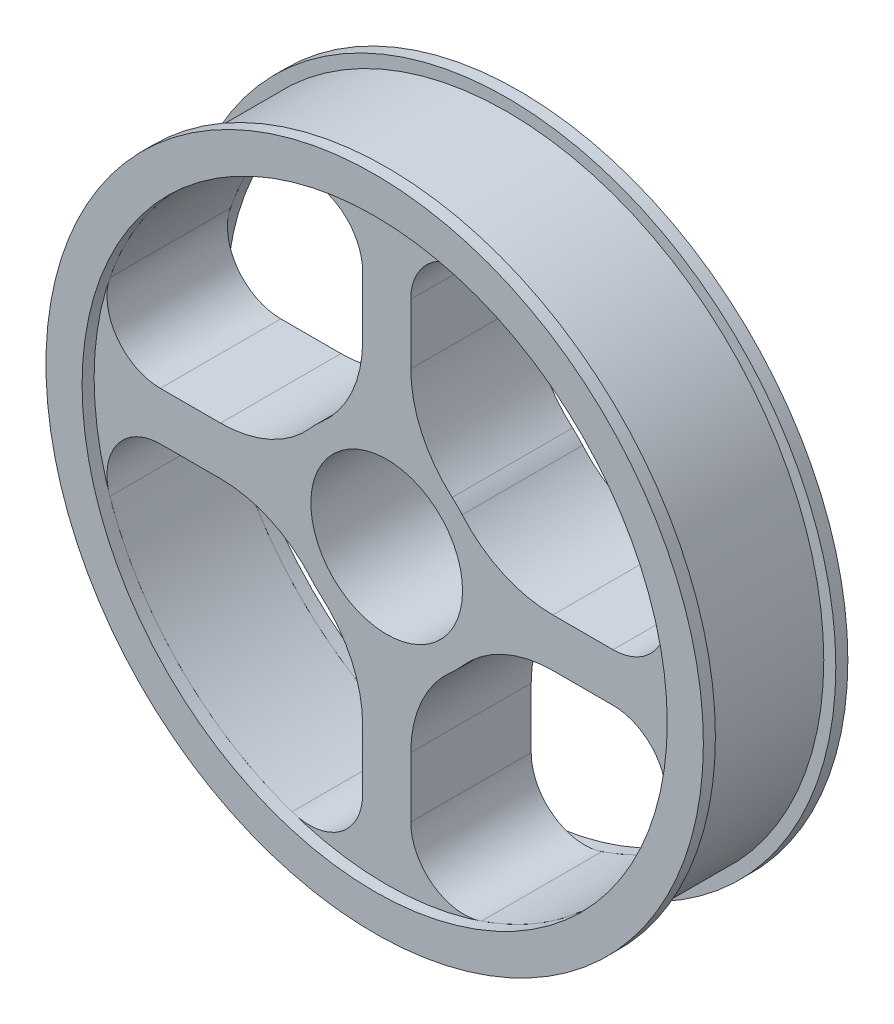
SolidWorks part; units mm, degrees
material "ABS"
ref_plane "Front Plane" through (0, 0, 0) normal (0, 0, 1) x (1, 0, 0)
ref_plane "Top Plane" through (0, 0, 0) normal (0, 1, 0) x (1, 0, 0)
ref_plane "Right Plane" through (0, 0, 0) normal (1, 0, 0) x (0, 0, -1)
sketch "Sketch1" plane through (0, 0, 0) normal (0, 0, 1) x (1, 0, 0)
  line L0 (-14.5852, 8.4694) -> (-14.5852, 12.5334) construction
  line L2 (-14.0772, 11.1364) -> (-14.0772, 9.8664)
  line L4 (-15.0932, 11.1364) -> (-15.0932, 9.8664)
  line L5 (-9.8102, 6.8694) -> (-11.0802, 6.8694)
  line L6 (-14.5852, 10.5014) -> (-15.0932, 10.5014) construction
  line L7 (-9.8102, 5.8534) -> (-11.0802, 5.8534)
  line L8 (-14.0772, 1.5864) -> (-14.0772, 2.8564)
  line L9 (-15.0932, 1.5864) -> (-15.0932, 2.8564)
  line L10 (-19.3602, 5.8534) -> (-18.0902, 5.8534)
  line L11 (-19.3602, 6.8694) -> (-18.0902, 6.8694)
  circle A1 centre (-14.5852, 6.3614) radius 2.108
  circle A5 centre (-14.5852, 6.3614) radius 6.172
  circle A6 centre (-14.5852, 6.3614) radius 1.6
  circle A7 centre (-14.5852, 6.3614) radius 6.68
  circle A8 centre (-14.5852, 6.3614) radius 6.934
  arc A9 (-15.0932, 11.1364) -> (-16.5828, 12.2012) centre (-16.2185, 11.1364) ccw
  arc A10 (-15.0932, 9.8664) -> (-15.9661, 7.9541) centre (-17.6242, 9.8664) cw
  arc A11 (-14.0772, 9.8664) -> (-13.2042, 7.9541) centre (-11.5461, 9.8664) ccw
  arc A12 (-14.0772, 11.1364) -> (-12.5876, 12.2012) centre (-12.9518, 11.1364) cw
  arc A13 (-11.0802, 6.8694) -> (-12.9925, 7.7424) centre (-11.0802, 9.4005) cw
  arc A14 (-9.8102, 6.8694) -> (-8.7454, 8.359) centre (-9.8102, 7.9948) ccw
  arc A15 (-9.8102, 5.8534) -> (-8.7454, 4.3638) centre (-9.8102, 4.728) cw
  arc A16 (-11.0802, 5.8534) -> (-12.9925, 4.9804) centre (-11.0802, 3.3223) ccw
  arc A17 (-14.0772, 2.8564) -> (-13.2042, 4.7687) centre (-11.5461, 2.8564) cw
  arc A18 (-14.0772, 1.5864) -> (-12.5876, 0.5216) centre (-12.9518, 1.5864) ccw
  arc A19 (-15.0932, 1.5864) -> (-16.5828, 0.5216) centre (-16.2185, 1.5864) cw
  arc A20 (-15.0932, 2.8564) -> (-15.9661, 4.7687) centre (-17.6242, 2.8564) ccw
  arc A21 (-18.0902, 5.8534) -> (-16.1779, 4.9804) centre (-18.0902, 3.3223) cw
  arc A22 (-19.3602, 5.8534) -> (-20.425, 4.3638) centre (-19.3602, 4.728) ccw
  arc A23 (-19.3602, 6.8694) -> (-20.425, 8.359) centre (-19.3602, 7.9948) cw
  arc A24 (-18.0902, 6.8694) -> (-16.1779, 7.7424) centre (-18.0902, 9.4005) ccw
  circle A27 centre (-14.5852, 6.3614) radius 1.6 construction
  point P4 (-15.9228, 6.2618)
  point P22 (-13.5497, 5.29)
  point P64 (-14.5852, 6.3614)
  dimension "D1" = 0.508
  dimension "D2" = 0.508
  dimension "D3" = 5.08
  dimension "D4" = 0.254
  dimension "D5" = 0.508
  dimension "D6" = 1.27
  dimension "D7" = 4
extrude "Boss-Extrude1" add sketch "Sketch1" along normal mid plane 2.54 contours A7 A5 | L2 A12 A5 A9 L4 A10 A1 A11 | A16 L7 A15 A5 A14 L5 A13 A1 | A24 L11 A23 A5 A22 L10 A21 A1 | A20 L9 A19 A5 A18 L8 A17 A1 | A1 A6 region at (-14.5852, 10.5868, 0) region at (-13.1368, 7.8098, 0) region at (-10.3598, 6.3614, 0) region at (-18.8106, 6.3614, 0) region at (-14.5852, 2.136, 0) region at (-21.0762, 6.3614, 0)
extrude "Boss-Extrude2" add sketch "Sketch1<5>" along normal blind 0.254 from surface separate body contours A7 A5 | A8 A7 region at (-21.0762, 6.3614, 0) region at (-21.3231, 6.3614, 0) starting at face at (-12.0398, 3.816, 1.27)
sketch "Sketch1<5>" plane through (0, 0, 0) normal (0, 0, 1) x (1, 0, 0) same geometry as "Sketch1"
mirror "Mirror2" about plane through (0, 0, 0) normal (0, 0, 1) of bodies 105 102
